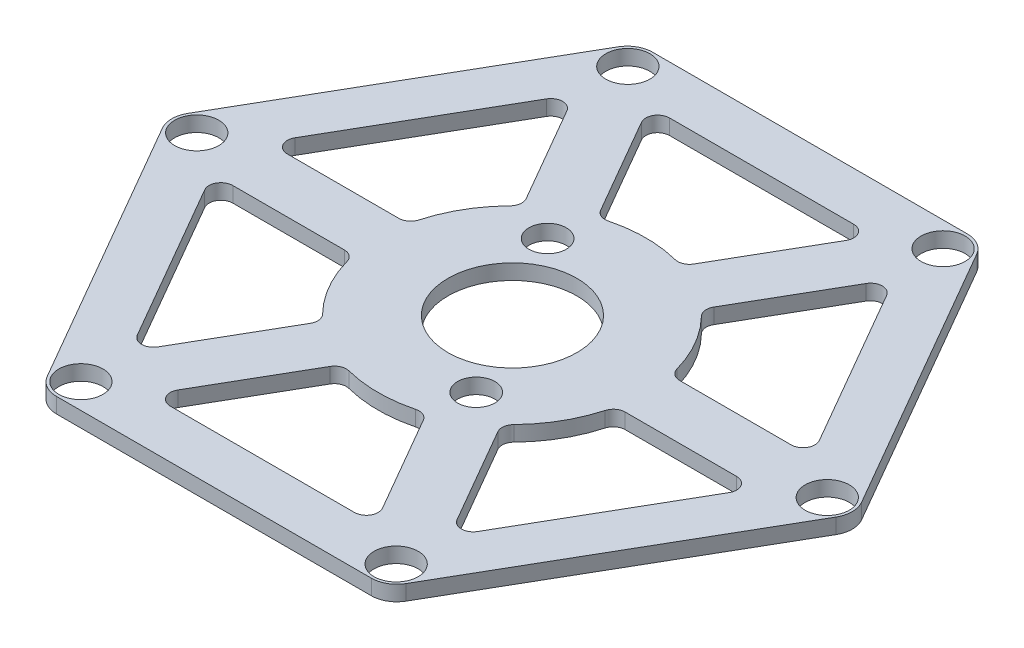
SolidWorks part; units mm, degrees
ref_plane "Front Plane" through (0, 0, 0) normal (0, 0, 1) x (1, 0, 0)
ref_plane "Top Plane" through (0, 0, 0) normal (0, 1, 0) x (1, 0, 0)
ref_plane "Right Plane" through (0, 0, 0) normal (1, 0, 0) x (0, 0, -1)
sketch "Sketch1" plane through (0, 0, 0) normal (0, 1, 0) x (1, 0, 0)
  line L1 (-20.3, 35.1606) -> (-40.6, 0)
  line L2 (-40.6, 0) -> (-20.3, -35.1606)
  line L3 (-20.3, -35.1606) -> (20.3, -35.1606)
  line L4 (20.3, -35.1606) -> (40.6, 0)
  line L5 (40.6, 0) -> (20.3, 35.1606)
  line L6 (20.3, 35.1606) -> (-20.3, 35.1606)
  line L7 (-17, 29.4449) -> (-34, 0)
  line L8 (-34, 0) -> (-17, -29.4449)
  line L9 (-17, -29.4449) -> (17, -29.4449)
  line L10 (17, -29.4449) -> (34, 0)
  line L11 (34, 0) -> (17, 29.4449)
  line L12 (17, 29.4449) -> (-17, 29.4449)
  line L13 (-18.6638, 32.2165) -> (-37.3656, -0.0563) construction
  line L14 (-37.3656, -0.0563) -> (-18.7674, -32.3889) construction
  line L15 (-18.7674, -32.3889) -> (18.5325, -32.4487) construction
  line L16 (18.5325, -32.4487) -> (37.3, 0) construction
  line L17 (37.3, 0) -> (18.6362, 32.2165) construction
  line L18 (18.6362, 32.2165) -> (-18.6638, 32.2165) construction
  line L50 (-17, 29.4449) -> (17, -29.4449) construction
  line L51 (-17, 29.4449) -> (-18.8579, 26.2268)
  line L56 (-13.2841, 29.4449) -> (-17, 29.4449)
  line L57 (-13.3543, 16.6943) -> (-7.7805, 19.9123) construction
  line L58 (-17, 29.4449) -> (-13.2841, 29.4449)
  line L59 (-13.2841, 29.4449) -> (-4.9475, 15.0054)
  line L60 (-17, 29.4449) -> (-18.8579, 26.2268)
  line L61 (-18.8579, 26.2268) -> (-10.5213, 11.7874)
  line L62 (17, 29.4449) -> (13.2841, 29.4449)
  line L63 (13.2841, 29.4449) -> (4.9475, 15.0054)
  line L66 (18.8579, 26.2268) -> (10.5213, 11.7874)
  line L67 (17, 29.4449) -> (18.8579, 26.2268)
  line L68 (34, 0) -> (32.1421, 3.2181)
  line L69 (32.1421, 3.2181) -> (15.4688, 3.2181)
  line L72 (32.1421, -3.2181) -> (15.4688, -3.2181)
  line L73 (34, 0) -> (32.1421, -3.2181)
  line L74 (17, -29.4449) -> (18.8579, -26.2268)
  line L75 (18.8579, -26.2268) -> (10.5213, -11.7874)
  line L78 (13.2841, -29.4449) -> (4.9475, -15.0054)
  line L79 (17, -29.4449) -> (13.2841, -29.4449)
  line L80 (-17, -29.4449) -> (-13.2841, -29.4449)
  line L81 (-13.2841, -29.4449) -> (-4.9475, -15.0054)
  line L84 (-18.8579, -26.2268) -> (-10.5213, -11.7874)
  line L85 (-17, -29.4449) -> (-18.8579, -26.2268)
  line L86 (-34, 0) -> (-32.1421, -3.2181)
  line L87 (-32.1421, -3.2181) -> (-15.4688, -3.2181)
  line L90 (-32.1421, 3.2181) -> (-15.4688, 3.2181)
  line L91 (-34, 0) -> (-32.1421, 3.2181)
  line L92 (18.6362, 32.2165) -> (31.4889, 27.5601) construction
  circle A0 centre (0.0529, 0) radius 7.6
  circle A2 centre (0.0529, 0) radius 11.5 construction
  circle A3 centre (-5.7367, 9.9363) radius 2.2
  arc A4 (-10.5213, 11.7874) -> (-15.4688, 3.2181) centre (0, 0) ccw
  arc A5 (4.9475, 15.0054) -> (-4.9475, 15.0054) centre (0, 0) ccw
  arc A6 (15.4688, 3.2181) -> (10.5213, 11.7874) centre (0, 0) ccw
  arc A7 (10.5213, -11.7874) -> (15.4688, -3.2181) centre (0, 0) ccw
  arc A8 (-4.9475, -15.0054) -> (4.9475, -15.0054) centre (0, 0) ccw
  arc A9 (-15.4688, -3.2181) -> (-10.5213, -11.7874) centre (0, 0) ccw
  circle A10 centre (5.7632, -9.9821) radius 2.2
  circle A16 centre (18.6362, 32.2165) radius 2.6
  circle A17 centre (37.2184, -0.0312) radius 2.6
  circle A18 centre (18.5822, -32.2477) radius 2.6
  circle A19 centre (-18.6362, -32.2165) radius 2.6
  circle A20 centre (-37.2184, 0.0312) radius 2.6
  circle A21 centre (-18.5822, 32.2477) radius 2.6
  point P40 (0, 0)
  point P42 (0, 0)
  point P58 (0.0529, 0)
  point P59 (0, 0)
  point P62 (0, 0)
  point P77 (0, 0)
  point P82 (0, 0)
  point P92 (0, 0)
  dimension "D7" = 6
  dimension "D5" = 40
  dimension "D6" = 5.2
  dimension "D1" = 40.6
  dimension "D2" = 6.6
  dimension "D3" = 3.3
  dimension "D4" = 6
extrude "Boss-Extrude1" add sketch "Sketch1" along normal blind 1.8 contours L5 L6 L1 L2 L3 L4 L12 L11 L10 L9 | L87 A9 L84 L8 L9 L81 A8 L78 L10 L75 A7 L72 L11 L69 A6 L66 L12 L63 A5 L59 L7 L61 A4 L90 region at (0, 0, -34.0865) region at (-15.1421, 0, -28.5453)
fillet "Fillet1" radius 3 6 edges at (-40.6, 0.9, 0) (-20.3, 0.9, 35.1606) (20.3, 0.9, 35.1606) (40.6, 0.9, 0) (20.3, 0.9, -35.1606) (-20.3, 0.9, -35.1606)
fillet "Fillet2" radius 1.4 24 edges at (-32.1421, 0.9, 3.2181) (-15.4688, 0.9, 3.2181) (-10.5213, 0.9, 11.7874) (-18.8579, 0.9, 26.2268) (-13.2841, 0.9, 29.4449) (13.2841, 0.9, 29.4449) (-4.9475, 0.9, 15.0054) (4.9475, 0.9, 15.0054) (18.8579, 0.9, 26.2268) (10.5213, 0.9, 11.7874) (15.4688, 0.9, 3.2181) (32.1421, 0.9, 3.2181) (32.1421, 0.9, -3.2181) (18.8579, 0.9, -26.2268) (15.4688, 0.9, -3.2181) (10.5213, 0.9, -11.7874) (-32.1421, 0.9, -3.2181) (-15.4688, 0.9, -3.2181) (-4.9475, 0.9, -15.0054) (-13.2841, 0.9, -29.4449) (4.9475, 0.9, -15.0054) (13.2841, 0.9, -29.4449) (-10.5213, 0.9, -11.7874) (-18.8579, 0.9, -26.2268)
ref_plane "Plane1" through (0, 1.8, 0) normal (0, 1, 0) x (1, 0, 0)
scale "Scale1" scale about centroid uniform scaling yes scale factor 1.15
